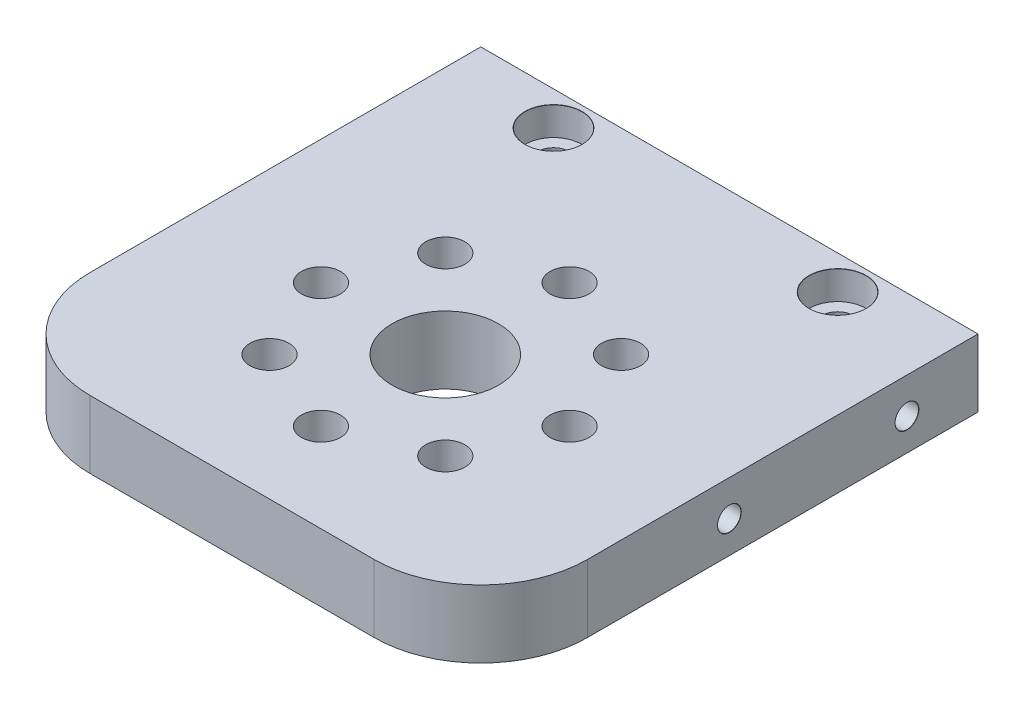
SolidWorks part; units mm, degrees
material "1060 Alloy"
ref_plane "Front Plane" through (0, 0, 0) normal (0, 0, 1) x (1, 0, 0)
ref_plane "Top Plane" through (0, 0, 0) normal (0, 1, 0) x (1, 0, 0)
ref_plane "Right Plane" through (0, 0, 0) normal (1, 0, 0) x (0, 0, -1)
sketch "Sketch1" plane through (0, 0, 0) normal (0, 1, 0) x (1, 0, 0)
  line L1 (-35, -35) -> (35, -35)
  line L2 (-35, -35) -> (-35, 35)
  line L3 (-35, 35) -> (35, 35)
  line L4 (35, -35) -> (35, 35)
  line L5 (-35, -35) -> (35, 35) construction
  line L6 (-35, 35) -> (35, -35) construction
  point P0 (0, 0)
  dimension "D1" = 70
  dimension "D2" = 70
extrude "Boss-Extrude1" add sketch "Sketch1" along normal blind 9.525
sketch "Sketch2" plane through (0, 0, 0) normal (0, -1, 0) x (1, 0, 0)
  line L1 (-35, 35) -> (35, 35) construction
  line L2 (-35, -35) -> (-35, 35) construction
  circle A0 centre (0, 5) radius 17.5 construction
  point P2 (0, 0)
  point P4 (0, 22.5)
  point P6 (12.3744, 17.3744)
  point P7 (17.5, 5)
  point P8 (12.3744, -7.3744)
  point P9 (0, -12.5)
  point P10 (-12.3744, -7.3744)
  point P11 (-17.5, 5)
  point P12 (-12.3744, 17.3744)
  point P13 (0, 5)
  dimension "D2" = 35
  dimension "D3" = 30
  dimension "D4" = 35
  dimension "D1" = 8
hole_wizard "CBORE for M5 SHCS2" positions "Sketch3" profile "Sketch4" counterbore size "M5" standard "ANSI Metric" end condition through all
sketch "Sketch3" plane through (0, 0, 0) normal (0, -1, 0) x (-1, 0, 0)
  point P0 (0, -22.5)
  point P3 (-12.3744, -17.3744)
  point P6 (-17.5, -5)
  point P9 (-12.3744, 7.3744)
  point P12 (0, 12.5)
  point P15 (12.3744, 7.3744)
  point P18 (17.5, -5)
  point P21 (12.3744, -17.3744)
sketch "Sketch4" plane through (0, 0, 22.5) normal (1, 0, 0) x (0, 0, -1)
  line L0 (0, 0) -> (0, 9.525)
  line L1 (0, 9.525) -> (2.75, 9.525)
  line L3 (2.75, 9.525) -> (2.75, 5)
  line L4 (5, 5) -> (2.75, 5)
  line L5 (5, 5) -> (5, 0.025)
  line L6 (5, 0.025) -> (5.025, 0)
  line L7 (5.025, 0) -> (0, 0)
  line L8 (-5, 0.025) -> (-5.025, 0) construction
  line L11 (0, -6.35) -> (0, 107.95) construction
  dimension "Thru Hole Dia." = 5.5
  dimension "Thru Hole Depth" = 9.525
  dimension "C'Bore Dia." = 10
  dimension "C'Bore Depth" = 5
  dimension "Near C'Sink Dia." = 10.05
  dimension "Near C'Sink Angle" = 90
sketch "Sketch5" plane through (35, 0, 0) normal (1, 0, 0) x (0, 0, -1)
  line L0 (35, 4.5) -> (-35, 4.5) construction
  line L1 (35, 9.525) -> (35, 0) construction
  line L3 (-35, 0) -> (35, 0) construction
  point P6 (25, 4.5)
  point P7 (0, 4.5)
  dimension "D1" = 10
  dimension "D2" = 25
  dimension "D3" = 4.5
hole_wizard "Tap Drill for M4x0.7 Tap1" positions "Sketch6" profile "Sketch8" hole size "M4x0.7" standard "ANSI Metric"
sketch "Sketch6" plane through (35, 0, 0) normal (1, 0, 0) x (0, 0, -1)
  point P0 (0, 4.5)
  point P3 (25, 4.5)
sketch "Sketch8" plane through (35, 4.5, 0) normal (0, 1, 0) x (0, 0, -1)
  line L0 (0, 0) -> (0, 8.9914)
  line L1 (0, 8.9914) -> (1.65, 8)
  line L2 (1.65, 8) -> (1.65, 0.025)
  line L3 (1.65, 0.025) -> (1.675, 0)
  line L5 (1.675, 0) -> (0, 0)
  line L6 (-1.65, 0.025) -> (-1.675, 0) construction
  line L10 (0, 8.9914) -> (-1.65, 8) construction
  line L11 (0, -6.35) -> (0, 107.95) construction
  dimension "Hole Dia." = 3.3
  dimension "Hole Depth" = 8
  dimension "Near C'Sink Dia." = 3.35
  dimension "Near C'Sink Angle" = 90
  dimension "Drill Angle" = 118
sketch "Sketch9" plane through (0, 0, 0) normal (0, -1, 0) x (1, 0, 0)
  circle A0 centre (0, 5) radius 7.5
  circle A1 centre (0, 5) radius 17.5 construction
  dimension "D1" = 15
extrude "Cut-Extrude1" cut sketch "Sketch9" against normal through all
sketch "Sketch10" plane through (0, 9.525, 0) normal (0, -1, 0) x (1, 0, 0)
  line L0 (35, -30.2375) -> (-35, -30.2375) construction
  line L1 (35, 35) -> (35, -35) construction
  line L2 (-35, -35) -> (-35, 35) construction
  line L3 (35, -35) -> (-35, -35) construction
  line L4 (0, -5.2388) -> (0, 5.2388) construction
  point P8 (20, -30.2375)
  point P11 (-20, -30.2375)
  dimension "D1" = 4.7625
  dimension "D2" = 15
hole_wizard "CBORE for M4 SHCS1" positions "Sketch14" profile "Sketch15" counterbore size "M4" standard "ANSI Metric" end condition through all
sketch "Sketch14" plane through (0, 9.525, 0) normal (0, 1, 0) x (1, 0, 0)
  point P0 (-20, 30.2375)
  point P3 (20, 30.2375)
sketch "Sketch15" plane through (-20, 9.525, -30.2375) normal (1, 0, 0) x (0, 0, 1)
  line L0 (0, 0) -> (0, 9.525)
  line L1 (0, 9.525) -> (2.25, 9.525)
  line L3 (2.25, 9.525) -> (2.25, 4)
  line L4 (4, 4) -> (2.25, 4)
  line L5 (4, 4) -> (4, 0.025)
  line L6 (4, 0.025) -> (4.025, 0)
  line L7 (4.025, 0) -> (0, 0)
  line L8 (-4, 0.025) -> (-4.025, 0) construction
  line L11 (0, -6.35) -> (0, 107.95) construction
  dimension "Thru Hole Dia." = 4.5
  dimension "Thru Hole Depth" = 9.525
  dimension "C'Bore Dia." = 8
  dimension "C'Bore Depth" = 4
  dimension "Near C'Sink Dia." = 8.05
  dimension "Near C'Sink Angle" = 90
mirror "Mirror1" about plane through (0, 0, 0) normal (1, 0, 0) of "Tap Drill for M4x0.7 Tap1"
fillet "Fillet1" radius 15 2 edges at (-35, 4.7625, 35) (35, 4.7625, 35)
ref_axis "Axis1" through (0, 0, 5) along (0, 1, 0)
